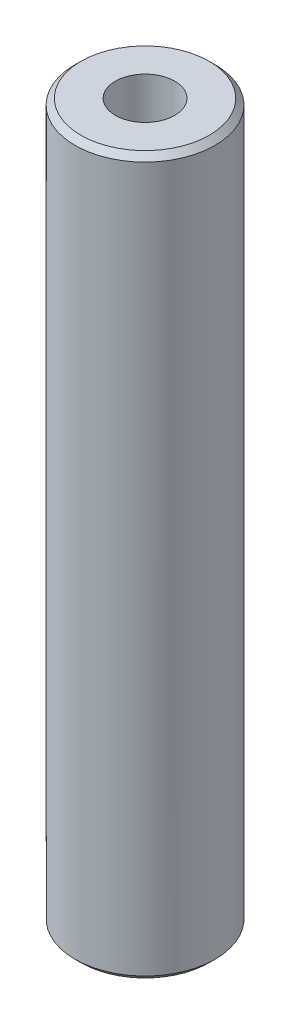
SolidWorks part; units mm, degrees
material "6061-T6 (SS)"
ref_plane "Alzado" through (0, 0, 0) normal (0, 0, 1) x (1, 0, 0)
ref_plane "Planta" through (0, 0, 0) normal (0, 1, 0) x (1, 0, 0)
ref_plane "Vista lateral" through (0, 0, 0) normal (1, 0, 0) x (0, 0, -1)
sketch "Croquis2" plane through (0, 0, 0) normal (0, 1, 0) x (1, 0, 0)
  circle A0 centre (0, 0) radius 4.7625
  dimension "D1" = 9.525
extrude "Saliente-Extruir1" add sketch "Croquis2" along normal mid plane 48.768
chamfer "Chaflán1" distance 0.3969 angle 45 2 edges at (0, -24.384, 4.7625) (0, 24.384, 4.7625)
sketch "Croquis3" plane through (0, 0, 0) normal (0, 1, 0) x (1, 0, 0)
  circle A0 centre (0, 0) radius 2.0193
  dimension "D1" = 4.0386
extrude "Tap Hole 1" cut sketch "Croquis3" against normal blind 19.05 from surface starting at face at (0, 24.384, 4.3656)
extrude "Tap Hole 2" cut sketch "Croquis3<2>" along normal blind 19.05 from surface starting at face at (0, -24.384, 4.3656)
sketch "Croquis3<2>" plane through (0, 0, 0) normal (0, 1, 0) x (1, 0, 0) same geometry as "Croquis3"
sketch "Croquis4" plane through (0, 0, 0) normal (0, 1, 0) x (1, 0, 0)
  circle A0 centre (0, 0) radius 2.4892
  dimension "D1" = 4.9784
extrude "Clearance Hole" [suppressed] cut sketch "Croquis4" against normal through all both and the other way through all
equation "\"OD\"= 0.375pulgadas"
equation "\"Largo\"= 1.92pulgadas"
equation "\"Tap Hole\"= IIF ( \"OD\" = 0.375pulgadas , 0.1590pulgadas , 0.201pulgadas )"
equation "\"Spacer Hole\"= IIF ( \"OD\" = 0.375pulgadas , 0.196pulgadas , 0.257pulgadas )"
equation "\"D1@Croquis2\"=\"OD\""
equation "\"D1@Saliente-Extruir1\"=\"Largo\""
equation "\"D1@Croquis3\"=\"Tap Hole\""
equation "\"D1@Croquis4\"=\"Spacer Hole\""
